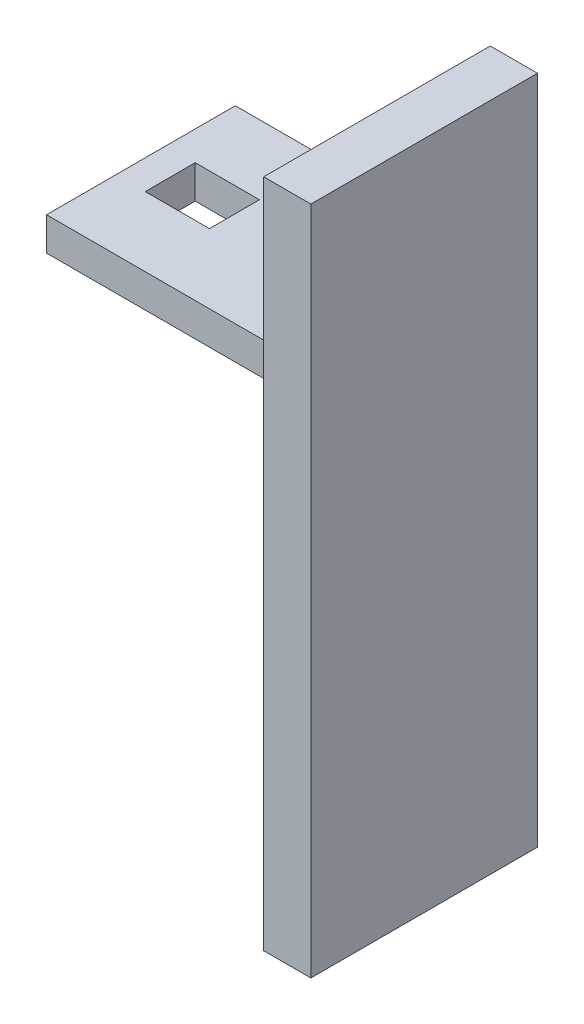
SolidWorks part; units mm, degrees
ref_plane "Front Plane" through (0, 0, 0) normal (1, 0, 0) x (0, 1, 0)
ref_plane "Top Plane" through (0, 0, 0) normal (0, 0, 1) x (0, 1, 0)
ref_plane "Right Plane" through (0, 0, 0) normal (0, 1, 0) x (-1, 0, 0)
sketch "Sketch2" plane through (0, 0, 0) normal (1, 0, 0) x (0, 1, 0)
  line L0 (45.5, 24) -> (18.7, 24) construction
  line L1 (-31.5, 24) -> (110.5095, 24)
  line L2 (-31.5, 24) -> (-31.5, -24)
  line L3 (-31.5, -24) -> (110.5095, -24)
  line L4 (110.5095, 24) -> (110.5095, -24)
  line L5 (-31.5, 24) -> (110.5095, -24) construction
  line L6 (-31.5, -24) -> (110.5095, 24) construction
  line L11 (-31.5, 6) -> (-31.5, -6) construction
  point P0 (6.1229, -11.2832)
  dimension "D1" = 0
  dimension "D2" = 0
extrude "Boss-Extrude1" add sketch "Sketch2" along normal blind 10
sketch "Sketch3" plane through (0, 0, 0) normal (-1, 0, 0) x (0, -1, 0)
  circle A0 centre (-14, 13) radius 2.65
  circle A1 centre (13.9762, 13) radius 2.65
  circle A2 centre (13.9762, -13) radius 2.65
  circle A3 centre (-14, -13) radius 2.65
  point P0 (13.9762, 13)
  point P1 (13.9762, -13)
  point P2 (-14, -13)
  point P3 (-14, 13)
  dimension "D1" = 5.3
  dimension "D2" = 5.3
  dimension "D3" = 5.3
  dimension "D4" = 5.3
extrude "Cut-Extrude1" cut sketch "Sketch3" against normal blind 7
sketch "Sketch4" plane through (0, 0, 0) normal (-1, 0, 0) x (0, -1, 0)
  line L0 (-65.5, 5) -> (-65.5, -5) construction
  line L1 (-69.5, 20) -> (-76.5473, 20)
  line L2 (-69.5, 20) -> (-69.5, -20)
  line L3 (-69.5, -20) -> (-76.5473, -20)
  line L4 (-76.5473, 20) -> (-76.5473, -20)
  line L5 (-69.5, 20) -> (-76.5473, -20) construction
  line L6 (-69.5, -20) -> (-76.5473, 20) construction
  line L7 (-110.5095, 24) -> (31.5, 24) construction
  line L8 (31.5, -24) -> (-110.5095, -24) construction
  point P0 (-73.0236, 0)
  dimension "D1" = 4
  dimension "D2" = 40
  dimension "D3" = 0
  dimension "D4" = 48
extrude "Boss-Extrude2" add sketch "Sketch4" along normal blind 50 and the other way blind 2
sketch "Sketch5" plane through (0, 76.5473, 0) normal (0, 1, 0) x (-1, 0, 0)
  line L1 (43.8, -5.3) -> (30.2, -5.3)
  line L2 (43.8, -5.3) -> (43.8, 5.3)
  line L3 (43.8, 5.3) -> (30.2, 5.3)
  line L4 (30.2, -5.3) -> (30.2, 5.3)
  line L5 (43.8, -5.3) -> (30.2, 5.3) construction
  line L6 (43.8, 5.3) -> (30.2, -5.3) construction
  point P0 (37, 0)
  dimension "D1" = 10.6
  dimension "D2" = 13.6
extrude "Cut-Extrude2" cut sketch "Sketch5" against normal up to surface (7.0473 mm away) up to face at (-25, 69.5, 0)
ref_plane "Plane1" through (0, 0, 0) normal (-1, 0, 0) x (0, 0, 1)
split "Split1" trim tools "Plane1" bodies to split 106 resulting bodies 107 108
sketch "Sketch8" plane through (0, 0, 0) normal (-1, 0, 0) x (0, -1, 0)
  line L1 (-69.25, 20.5) -> (-76.75, 20.5)
  line L2 (-69.25, 20.5) -> (-69.25, -20.5)
  line L3 (-69.25, -20.5) -> (-76.75, -20.5)
  line L4 (-76.75, 20.5) -> (-76.75, -20.5)
  line L5 (-69.25, 20.5) -> (-76.75, -20.5) construction
  line L6 (-69.25, -20.5) -> (-76.75, 20.5) construction
  point P0 (-73, 0)
  dimension "D1" = 7.5
  dimension "D2" = 41
  dimension "D3" = 7.5
  dimension "D4" = 0
extrude "Cut-Extrude3" cut sketch "Sketch8" against normal blind 2
